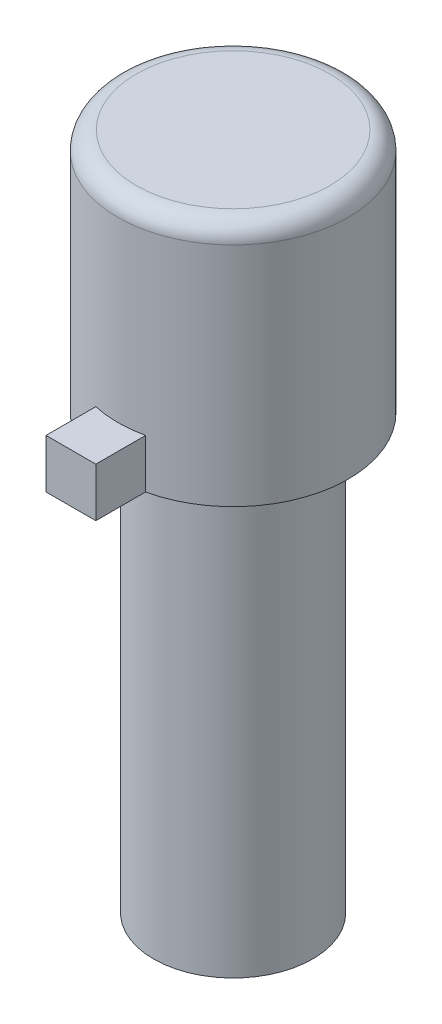
SolidWorks part; units mm, degrees
ref_plane "Front Plane" through (0, 0, 0) normal (0, 0, 1) x (1, 0, 0)
ref_plane "Top Plane" through (0, 0, 0) normal (0, 1, 0) x (1, 0, 0)
ref_plane "Right Plane" through (0, 0, 0) normal (1, 0, 0) x (0, 0, -1)
sketch "Sketch1" plane through (0, 0, 0) normal (0, 1, 0) x (1, 0, 0)
  circle A0 centre (0, 0) radius 3.25
  dimension "D1" = 6.5
extrude "Boss-Extrude1" add sketch "Sketch1" along normal blind 17.686 contours A0
sketch "Sketch2" plane through (0, 0, 0) normal (0, -1, 0) x (1, 0, 0)
  circle A1 centre (0, 0) radius 1.75
  dimension "D1" = 3.5
extrude "Cut-Extrude1" [suppressed] cut sketch "Sketch2" against normal blind 3.35
sketch "Sketch6" plane through (0, 17.686, 0) normal (0, 1, 0) x (1, 0, 0)
  circle A0 centre (0, 0) radius 4.7
  dimension "D1" = 9.4
extrude "Boss-Extrude2" add sketch "Sketch6" along normal blind 10 contours A0
fillet "Fillet1" radius 0.75 1 edges at (0, 27.686, 4.7)
sketch "Sketch7" plane through (0, 17.686, 0) normal (0, -1, 0) x (1, 0, 0)
  line L0 (0, 4.7) -> (0, -4.7) construction
  line L1 (-1.016, 4.5889) -> (-1.016, 6.6209)
  line L2 (-1.016, 6.6209) -> (1.016, 6.6209)
  line L3 (1.016, 6.6209) -> (1.016, 4.5889)
  circle A0 centre (0, 0) radius 4.7 construction
  circle A2 centre (0, 0) radius 4.7
  arc A3 (1.016, 4.5889) -> (-1.016, 4.5889) centre (0, 0) ccw
  point P7 (0, 0)
  dimension "D1" = 2.032
  dimension "D2" = 2.032
  dimension "D3" = 0
extrude "Boss-Extrude3" add sketch "Sketch7" against normal blind 2
